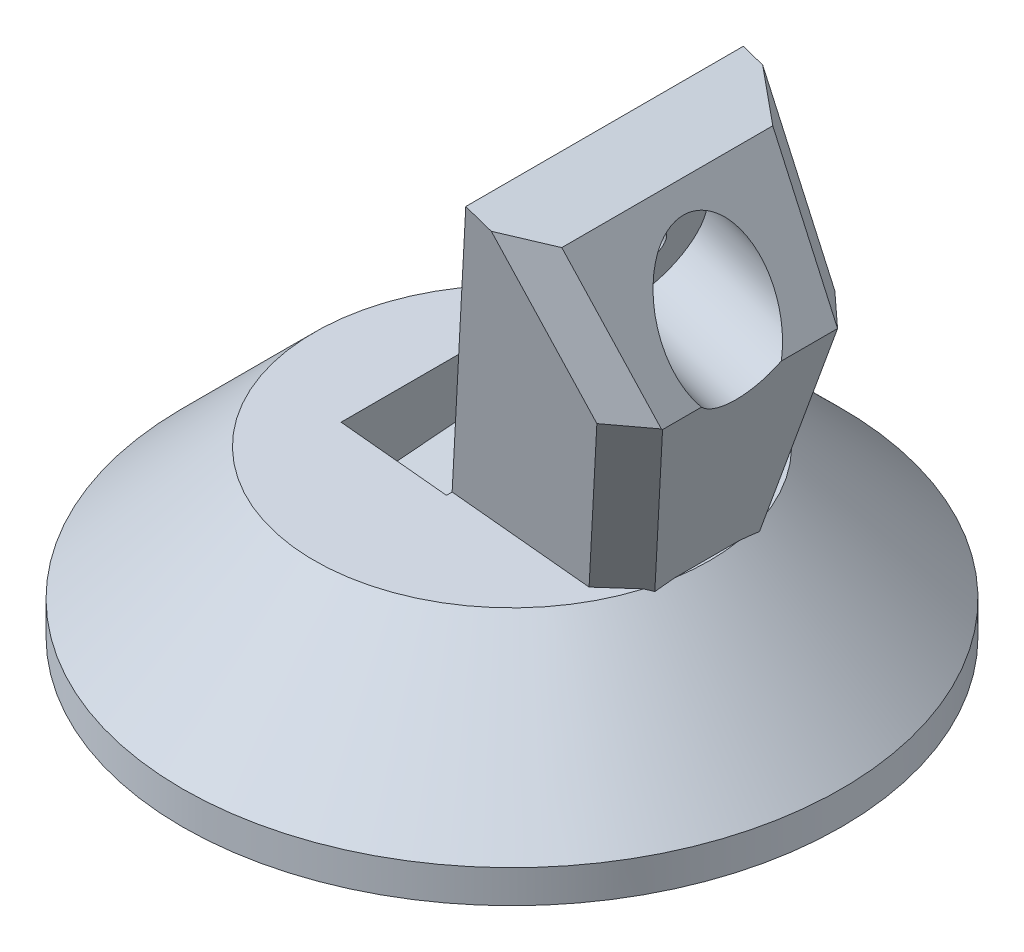
SolidWorks part; units mm, degrees
material "3D printed plastic"
ref_plane "Front Plane" through (0, 0, 0) normal (0, 0, 1) x (1, 0, 0)
ref_plane "Top Plane" through (0, 0, 0) normal (0, 1, 0) x (1, 0, 0)
ref_plane "Right Plane" through (0, 0, 0) normal (1, 0, 0) x (0, 0, -1)
sketch "Sketch1" plane through (0, 0, 0) normal (0, 0, 1) x (1, 0, 0)
  line L0 (-30, 0) -> (-30, 3)
  line L1 (-30, 3) -> (-18, 15)
  line L2 (-18, 15) -> (0, 15)
  line L3 (0, 15) -> (0, 0) construction
  line L4 (0, 0) -> (-30, 0)
  line L5 (0, 15) -> (0, 0)
  dimension "D1" = 60
  dimension "D2" = 3
  dimension "D3" = 15
  dimension "D4" = 45
revolve "Revolve1" add sketch "Sketch1" angle 360 about L3
ref_axis "Axis1" through (0, 0, -33) along (0, 0, 1)
ref_plane "Plane1" through (0, 0, 0) normal (0.9469, -0.3214, 0) x (0, 0, 1)
sketch "Sketch2" plane through (0, 0, 0) normal (0.9469, -0.3214, 0) x (0, 0, 1)
  line L0 (17.2648, -15.8407) -> (-17.2648, -15.8407) construction
  line L1 (8.4125, -19.9899) -> (3.1035, -1.426)
  line L2 (3.1035, -1.426) -> (-7.8024, -2.8617)
  line L3 (-7.8024, -2.8617) -> (-8.4125, -19.9899)
  line L4 (-8.4125, -19.9899) -> (8.4125, -19.9899)
  line L5 (0, -19.9899) -> (0, -23.5661) construction
  line L6 (-2.3495, -2.1439) -> (0, -19.9899) construction
  ellipse E0 centre (0, -14.204) end of major axis (-18, -14.204) minor radius 5.7859 construction
  dimension "D1" = 82.5
  dimension "D2" = 18
  dimension "D3" = 11
  dimension "D4" = 18
extrude "Cut-Extrude1" cut sketch "Sketch2" against normal blind 10 from offset 4 offset against normal yes
sketch "Sketch3" plane through (-3.7877, 1.2858, 0) normal (-0.9469, 0.3214, 0) x (0, 0, 1)
  line L0 (-7.6963, 14.4828) -> (-8.9431, 49.4828)
  line L1 (6.8376, 14.4828) -> (-8.2164, 14.4828) construction
  line L2 (-8.9431, 49.4828) -> (16.3272, 49.4828)
  line L3 (16.3272, 49.4828) -> (6.3175, 14.4828)
  line L4 (6.3175, 14.4828) -> (-7.6963, 14.4828)
  line L5 (6.8376, 14.4828) -> (3.1035, 1.426) construction
  line L6 (-7.8024, 2.8617) -> (-8.2164, 14.4828) construction
  line L7 (-0.6894, 14.4828) -> (-2.3495, 2.1439) construction
  line L8 (3.1035, 1.426) -> (-7.8024, 2.8617) construction
  line L9 (-8.2164, 14.4828) -> (6.8376, 14.4828) construction
  dimension "D1" = 0.5
  dimension "D2" = 35
extrude "Boss-Extrude1" add sketch "Sketch3" against normal blind 16
chamfer "Chamfer3" distance 10 angle 45 1 edges at (27.2689, 42.9995, 3.692)
chamfer "Chamfer1" distance 3 angle 45 4 edges at (20.7253, 23.7227, -8.2179) (20.74, 23.7659, 10.5183) (20.9271, 39.8721, -8.765) (20.9271, 39.8721, 14.8972) first distance on face at (19.7456, 20.8367, 1.5678) first distance on face at (20.9271, 39.8721, 3.0661)
sketch "Sketch4" plane through (0, 0, 0) normal (0, -1, 0) x (1, 0, 0)
  line L0 (-16, 0) -> (16, 0) construction
  circle A0 centre (-16, 0) radius 1.75
  circle A1 centre (16, 0) radius 1.75
  dimension "D2" = 3.5
  dimension "D1" = 32
extrude "Cut-Extrude2" cut sketch "Sketch4" against normal blind 11
sketch "Sketch5" plane through (11.3632, -3.8573, 0) normal (0.9469, -0.3214, 0) x (0, 0, -1)
  line L0 (-3.176, 42.9141) -> (0, 0) construction
  line L1 (-2.9031, 19.9141) -> (2.9031, 19.9141) construction
  line L2 (-3.6622, 49.4828) -> (-3.176, 42.9141) construction
  line L3 (-13.2664, 49.4828) -> (5.9421, 49.4828) construction
  circle A0 centre (-3.176, 42.9141) radius 1.5
  dimension "D1" = 3
  dimension "D2" = 23
extrude "Cut-Extrude3" cut sketch "Sketch5" against normal through all
sketch "Sketch6" plane through (11.3632, -3.8573, 0) normal (0.9469, -0.3214, 0) x (0, 0, -1)
  circle A0 centre (-3.176, 42.9141) radius 5
  dimension "D1" = 10
extrude "Cut-Extrude4" cut sketch "Sketch6" against normal blind 10
